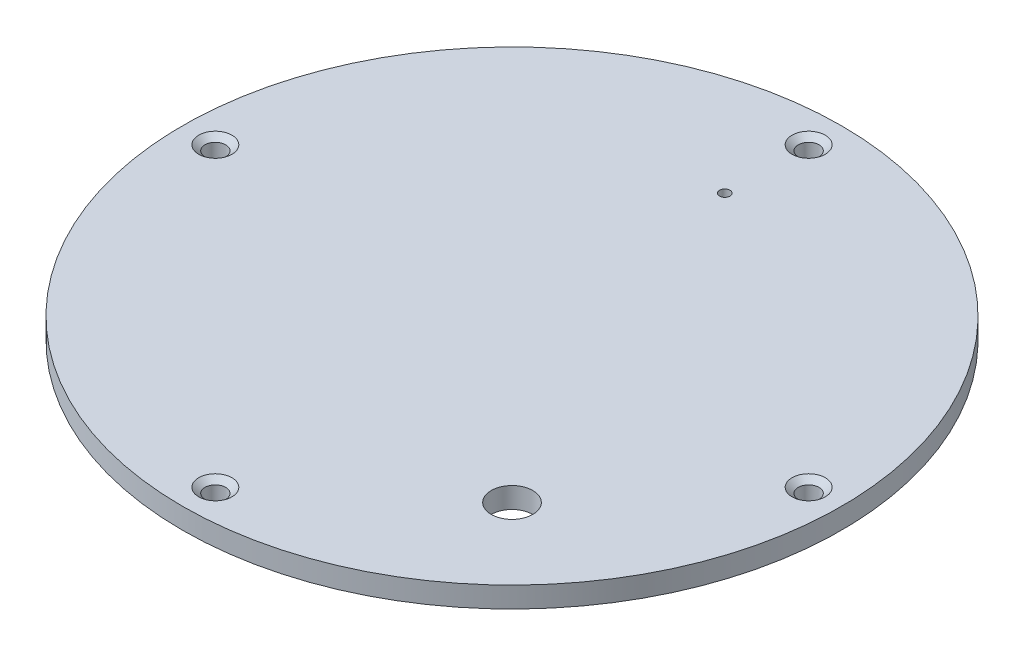
SolidWorks part; units mm, degrees
material "1060 Alloy"
ref_plane "Front Plane" through (0, 0, 0) normal (0, 0, 1) x (1, 0, 0)
ref_plane "Top Plane" through (0, 0, 0) normal (0, 1, 0) x (1, 0, 0)
ref_plane "Right Plane" through (0, 0, 0) normal (1, 0, 0) x (0, 0, -1)
sketch "Sketch1" plane through (0, 0, 0) normal (0, 1, 0) x (1, 0, 0)
  circle A0 centre (0, 0) radius 15.875
  dimension "D1" = 31.75
extrude "Boss-Extrude1" add sketch "Sketch1" along normal blind 1
hole_wizard "CSK for M2 Flat Head Machine Screw1" positions "Sketch2" profile "Sketch3" countersink size "M2" standard "ANSI Metric" end condition through all
sketch "Sketch2" plane through (0, 1, 0) normal (0, 1, 0) x (1, 0, 0)
  point P0 (0, 14.29)
  point P2 (14.29, 0)
  point P4 (0, -14.29)
  point P6 (-14.29, 0)
  dimension "D1" = 14.29
  dimension "D2" = 14.29
  dimension "D3" = 14.29
  dimension "D4" = 14.29
sketch "Sketch3" plane through (0, 1, -14.29) normal (1, 0, 0) x (0, 0, 1)
  line L0 (0, 0) -> (0, 1)
  line L1 (0, 1) -> (0.5, 1)
  line L2 (0.5, 1) -> (0.5, 0.2517)
  line L3 (0.5, 0.2517) -> (0.8, 0)
  line L5 (0.8, 0) -> (0, 0)
  line L6 (-0.5, 0.2517) -> (-0.8, 0) construction
  line L11 (0, -6.35) -> (0, 107.95) construction
  dimension "Thru Hole Dia." = 1
  dimension "Thru Hole Depth" = 1
  dimension "Near C'Sink Dia." = 1.6
  dimension "Near C'Sink Angle" = 100
sketch "Sketch4" plane through (0, 1, 0) normal (0, 1, 0) x (1, 0, 0)
  circle A0 centre (0, 10.25) radius 0.25
  dimension "D1" = 0.5
  dimension "D2" = 10.25
extrude "Cut-Extrude1" cut sketch "Sketch4" against normal through all both and the other way through all
sketch "Sketch5" plane through (0, 0, 0) normal (0, -1, 0) x (1, 0, 0)
  line L0 (0, 0) -> (12.768, 12.768) construction
  line L1 (0, 0) -> (24.3444, 0) construction
  circle A0 centre (7.7782, 7.7782) radius 1
  dimension "D2" = 2
  dimension "D1" = 11
  dimension "D3" = 45
extrude "Cut-Extrude2" cut sketch "Sketch5" against normal through all both and the other way through all
